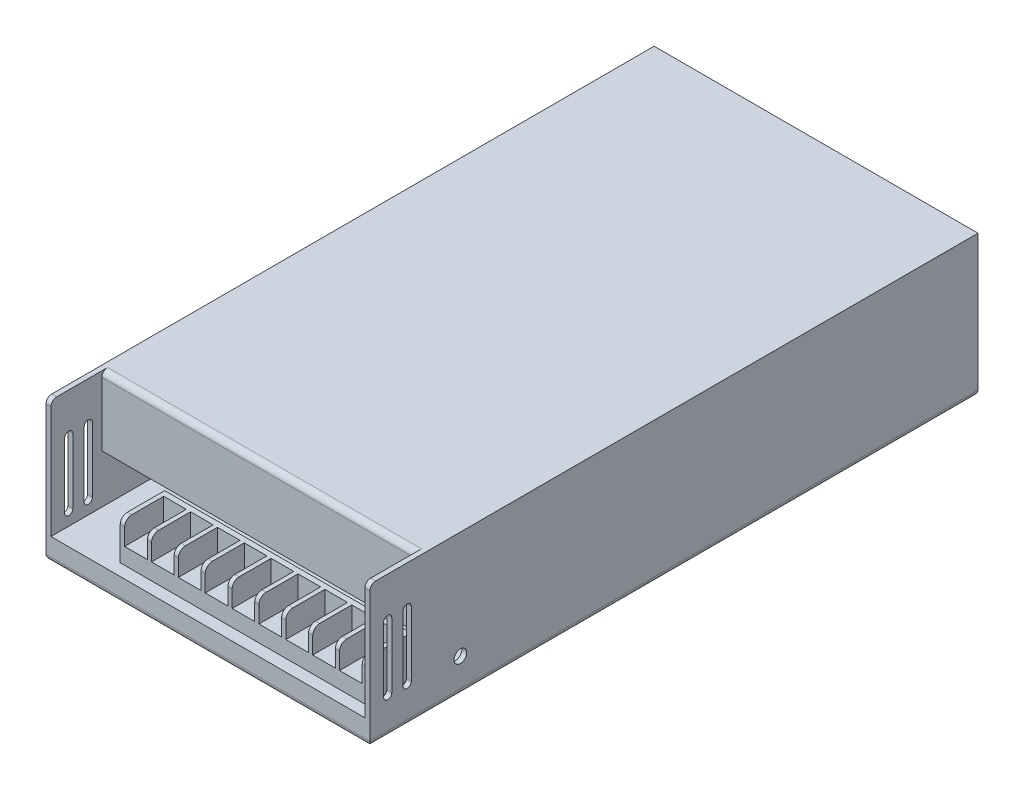
SolidWorks part; units mm, degrees
material "2024 Alloy"
ref_plane "Front Plane" through (0, 0, 0) normal (0, 0, 1) x (1, 0, 0)
ref_plane "Top Plane" through (0, 0, 0) normal (0, 1, 0) x (1, 0, 0)
ref_plane "Right Plane" through (0, 0, 0) normal (1, 0, 0) x (0, 0, -1)
sketch "Sketch1" plane through (0, 0, 0) normal (0, 1, 0) x (1, 0, 0)
  line L0 (0, 197) -> (0, -18) construction
  line L1 (-57.25, -18) -> (57.25, -18)
  line L2 (-57.25, -18) -> (-57.25, 197)
  line L3 (-57.25, 197) -> (57.25, 197)
  line L4 (57.25, -18) -> (57.25, 197)
  line L5 (-57.25, 0) -> (57.25, 0) construction
  dimension "D1" = 215
  dimension "D2" = 18
  dimension "D3" = 114.5
extrude "Boss-Extrude1" add sketch "Sketch1" along normal blind 41.75 and the other way blind 8.25
sketch "Sketch2" plane through (0, 0, 18) normal (0, 0, 1) x (1, 0, 0)
  line L0 (-57.25, 41.75) -> (57.25, 41.75) construction
  line L1 (-55.5, 0) -> (55.5, 0)
  line L2 (-55.5, 0) -> (-55.5, 41.75)
  line L3 (-55.5, 41.75) -> (55.5, 41.75)
  line L4 (55.5, 0) -> (55.5, 41.75)
  line L5 (0, 0) -> (0, 41.75) construction
  line L6 (57.25, -8.25) -> (57.25, 41.75) construction
  dimension "D1" = 1.75
extrude "Cut-Extrude1" cut sketch "Sketch2" against normal blind 18
sketch "Sketch3" plane through (57.25, 0, 0) normal (1, 0, 0) x (0, 0, -1)
  line L0 (-11.71, 27.7) -> (-11.71, 4.7) construction
  line L1 (-10.26, 27.7) -> (-10.26, 4.7)
  line L2 (-13.16, 27.7) -> (-13.16, 4.7)
  line L3 (-4.81, 27.7) -> (-4.81, 4.7) construction
  line L4 (-3.36, 27.7) -> (-3.36, 4.7)
  line L5 (-6.26, 27.7) -> (-6.26, 4.7)
  line L6 (-11.71, 16.2) -> (-4.81, 16.2) construction
  line L7 (-18, -8.25) -> (-18, 41.75) construction
  line L8 (-11.71, 29.15) -> (-11.71, 41.75) construction
  line L9 (-18, 41.75) -> (197, 41.75) construction
  line L10 (-11.71, 3.25) -> (-11.71, -8.25) construction
  line L11 (-18, -8.25) -> (197, -8.25) construction
  arc A0 (-10.26, 27.7) -> (-13.16, 27.7) centre (-11.71, 27.7) ccw
  arc A1 (-13.16, 4.7) -> (-10.26, 4.7) centre (-11.71, 4.7) ccw
  arc A2 (-3.36, 27.7) -> (-6.26, 27.7) centre (-4.81, 27.7) ccw
  arc A3 (-6.26, 4.7) -> (-3.36, 4.7) centre (-4.81, 4.7) ccw
  point P2 (-11.71, 16.2)
  point P7 (-4.81, 16.2)
  dimension "D1" = 4.84
  dimension "D2" = 2.9
  dimension "D3" = 4
  dimension "D4" = 12.6
  dimension "D5" = 11.5
extrude "Cut-Extrude2" cut sketch "Sketch3" against normal through all
fillet "Fillet1" radius 2 7 edges at (0, -8.25, -197) (-57.25, -8.25, -89.5) (0, -8.25, 18) (57.25, -8.25, -89.5) (0, 41.75, 0) (56.375, 41.75, 18) (-56.375, 41.75, 18)
sketch "Sketch4" plane through (0, 0, 0) normal (0, 1, 0) x (-1, 0, 0)
  line L0 (55.5, 0) -> (-55.5, 0) construction
  line L1 (35.2, 0) -> (-51.85, 0)
  line L2 (35.2, 0) -> (35.2, 13.8)
  line L3 (35.2, 13.8) -> (-51.85, 13.8)
  line L4 (-51.85, 0) -> (-51.85, 13.8)
  line L5 (55.5, 18) -> (-55.5, 18) construction
  line L6 (-55.5, 0) -> (-55.5, 18) construction
  line L7 (55.5, 0) -> (55.5, 18) construction
  dimension "D1" = 4.2
  dimension "D2" = 3.65
  dimension "D3" = 20.3
extrude "Boss-Extrude2" add sketch "Sketch4" along normal blind 14.25 separate body
sketch "Sketch7" plane through (0, 0, 0) normal (0, 0, 1) x (1, 0, 0)
  line L0 (-55.5, 39.75) -> (-55.5, 0) construction
  line L1 (-55.5, 17.25) -> (55.5, 17.25)
  line L2 (-55.5, 17.25) -> (-55.5, 0)
  line L3 (-55.5, 0) -> (55.5, 0)
  line L4 (55.5, 17.25) -> (55.5, 0)
  line L5 (-55.5, 0) -> (55.5, 0) construction
  line L6 (51.85, 14.25) -> (-35.2, 14.25) construction
  line L7 (55.5, 0) -> (55.5, 39.75) construction
  dimension "D1" = 3
extrude "Cut-Extrude4" cut sketch "Sketch7" against normal offset from surface (195.25 mm away) 1.75 up to face at (0, 17.75, -197)
fillet "Fillet2" radius 2.5 1 edges at (8.325, 14.25, 13.8)
sketch "Sketch6" plane through (0, 0, 13.8) normal (0, 0, 1) x (1, 0, 0)
  line L0 (-35.2, 14.25) -> (51.85, 14.25) construction
  line L1 (42.35, 14.25) -> (50.35, 14.25)
  line L2 (42.35, 14.25) -> (42.35, 5.8)
  line L3 (42.35, 5.8) -> (50.35, 5.8)
  line L4 (50.35, 14.25) -> (50.35, 5.8)
  line L6 (51.85, 11.75) -> (51.85, 0) construction
  line L7 (-35.2, 0) -> (51.85, 0) construction
  dimension "D1" = 5.8
  dimension "D2" = 1.5
  dimension "D3" = 8
extrude "Cut-Extrude3" cut sketch "Sketch6" against normal up to surface (13.8 mm away) up to face at (0, 28.5, 0)
sketch "Sketch9" plane through (0, 0, 0) normal (0, 0, -1) x (-1, 0, 0)
  line L0 (35.2, 14.25) -> (35.2, 0) construction
  line L1 (-51.85, 14.25) -> (35.2, 14.25)
  line L2 (-51.85, 14.25) -> (-51.85, 0.5)
  line L3 (-51.85, 0.5) -> (35.2, 0.5)
  line L4 (35.2, 14.25) -> (35.2, 0.5)
  line L5 (-51.85, 0) -> (35.2, 0) construction
  dimension "D1" = 0.5
extrude "Boss-Extrude6" add sketch "Sketch9" along normal blind 1.9
pattern_linear "LPattern1" count 9 spacing 9.5 along (1, 0, 0) of "Cut-Extrude3"
hole_wizard "M3 Clearance Hole2" positions "Sketch14" profile "Sketch13" hole size "M3" standard "Ansi Metric"
sketch "Sketch14" plane through (0, -8.25, 0) normal (0, -1, 0) x (1, 0, 0)
  line L0 (-57.25, 18) -> (57.25, 18) construction
  line L2 (-57.25, -197) -> (-57.25, 18) construction
  line L3 (57.25, -197) -> (-57.25, -197) construction
  line L4 (57.25, 18) -> (57.25, -197) construction
  point P0 (-47.5, -8.75)
  point P1 (47.5, -8.75)
  point P3 (47.5, -187.25)
  point P5 (-47.5, -187.25)
  dimension "D1" = 26.75
  dimension "D2" = 9.75
  dimension "D3" = 9.75
  dimension "D4" = 9.75
sketch "Sketch13" plane through (-47.5, -8.25, -8.75) normal (1, 0, 0) x (0, 0, -1)
  line L0 (0, 0) -> (0, 3.0215)
  line L1 (0, 3.0215) -> (1.7, 2)
  line L2 (1.7, 2) -> (1.7, 0)
  line L5 (1.7, 0) -> (0, 0)
  line L10 (0, 3.0215) -> (-1.7, 2) construction
  line L11 (0, -6.35) -> (0, 107.95) construction
  dimension "Hole Dia." = 3.4
  dimension "Hole Depth" = 2
  dimension "Drill Angle" = 118
hole_wizard "M4 Clearance Hole1" positions "Sketch16" profile "Sketch15" hole size "M4" standard "Ansi Metric"
sketch "Sketch16" plane through (57.25, 0, 0) normal (1, 0, 0) x (0, 0, -1)
  line L0 (-18, -6.25) -> (-18, 39.75) construction
  line L1 (195, -8.25) -> (-16, -8.25) construction
  point P0 (14, 3.75)
  dimension "D1" = 32
  dimension "D2" = 12
sketch "Sketch15" plane through (57.25, 3.75, -14) normal (0, 1, 0) x (0, 0, -1)
  line L0 (0, 0) -> (0, 3.3519)
  line L1 (0, 3.3519) -> (2.25, 2)
  line L2 (2.25, 2) -> (2.25, 0)
  line L5 (2.25, 0) -> (0, 0)
  line L10 (0, 3.3519) -> (-2.25, 2) construction
  line L11 (0, -6.35) -> (0, 107.95) construction
  dimension "Hole Dia." = 4.5
  dimension "Hole Depth" = 2
  dimension "Drill Angle" = 118
